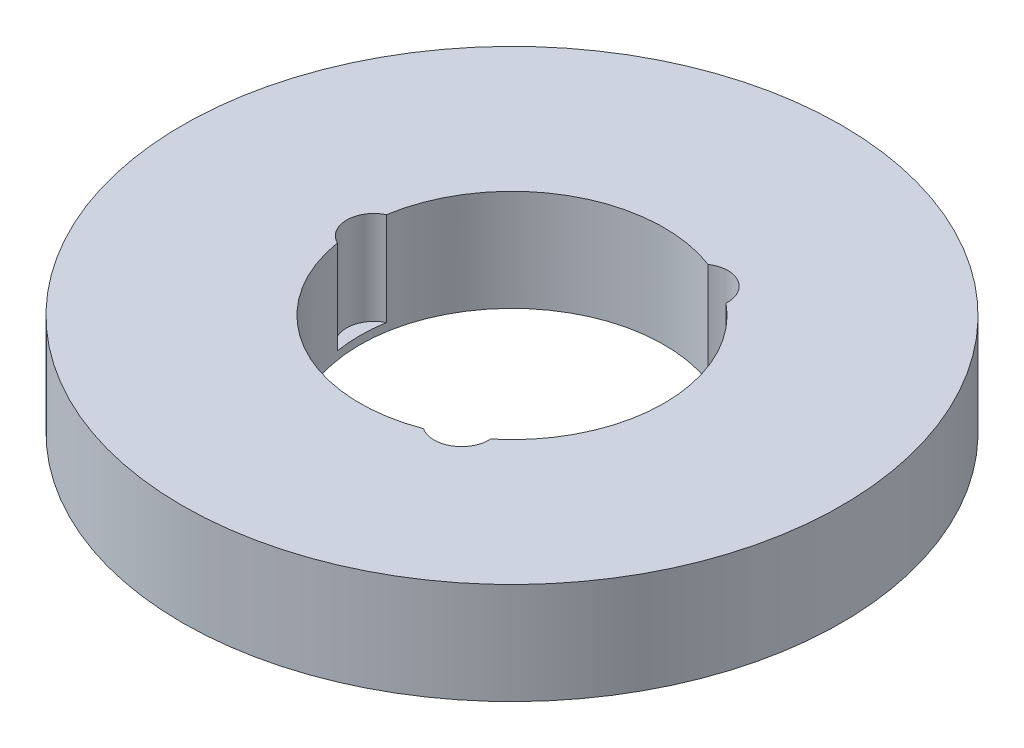
SolidWorks part; units mm, degrees
ref_plane "Front Plane" through (0, 0, 0) normal (0, 0, 1) x (1, 0, 0)
ref_plane "Top Plane" through (0, 0, 0) normal (0, 1, 0) x (1, 0, 0)
ref_plane "Right Plane" through (0, 0, 0) normal (1, 0, 0) x (0, 0, -1)
sketch "Sketch1" plane through (0, 0, 0) normal (0, 1, 0) x (1, 0, 0)
  circle A0 centre (0, 0) radius 97.5
  dimension "FLANGE_OD" = 195
extrude "Boss-Extrude1" add sketch "Sketch1" along normal blind 30
sketch "Sketch2" plane through (0, 0, 0) normal (0, 1, 0) x (1, 0, 0)
  circle A0 centre (0, 0) radius 45
  dimension "BORE_D" = 90
extrude "Cut-Extrude1" cut sketch "Sketch2" along normal through all
sketch "Sketch3" plane through (0, 30, 0) normal (0, 1, 0) x (1, 0, 0)
  circle A0 centre (0, 0) radius 40.8149 construction
  circle A1 centre (-40.8149, 0) radius 8.105
  dimension "BOLT_D" = 16.21
  dimension "BOLT_PCD" = 81.6297
extrude "Cut-Extrude2" cut sketch "Sketch3" against normal blind 27.6508
pattern_circular "CirPattern1" count 3 over 360 about axis through (0, 0, 0) along (0, 1, 0) of "Cut-Extrude2"
